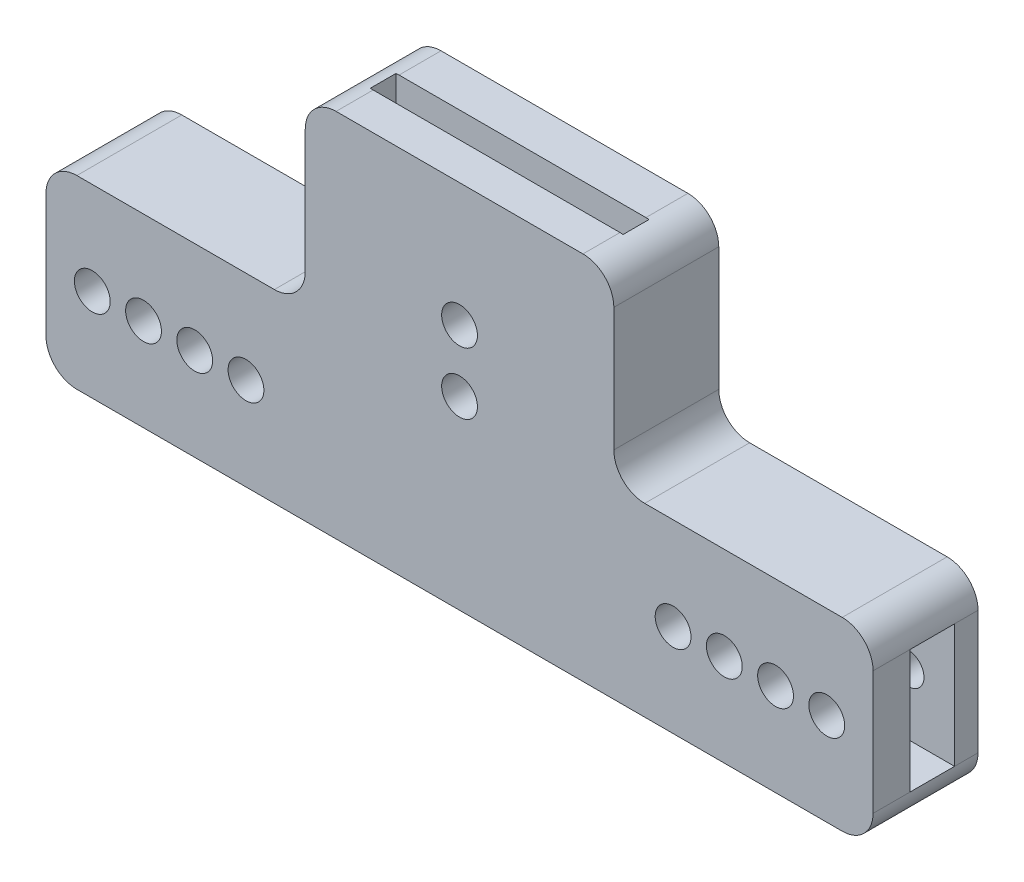
SolidWorks part; units mm, degrees
ref_plane "Front Plane" through (0, 0, 0) normal (0, 0, 1) x (1, 0, 0)
ref_plane "Top Plane" through (0, 0, 0) normal (0, 1, 0) x (1, 0, 0)
ref_plane "Right Plane" through (0, 0, 0) normal (1, 0, 0) x (0, 0, -1)
sketch "Sketch1" plane through (0, 0, 0) normal (0, 0, 1) x (1, 0, 0)
  line L1 (-25, 30) -> (25, 30)
  line L2 (-25, 30) -> (-25, -30)
  line L3 (-25, -30) -> (25, -30)
  line L4 (25, 30) -> (25, -30)
  line L5 (-25, 30) -> (25, -30) construction
  line L6 (-25, -30) -> (25, 30) construction
  point P0 (0, 0)
extrude "Boss-Extrude1" add sketch "Sketch1" along normal blind 12
sketch "Sketch2" plane through (0, 30, 0) normal (0, 1, 0) x (1, 0, 0)
  line L0 (0, 0) -> (0, -12) construction
  line L1 (-20.5, -6.8) -> (20.5, -6.8)
  line L2 (-20.5, -6.8) -> (-20.5, -11)
  line L3 (-20.5, -11) -> (20.5, -11)
  line L4 (20.5, -6.8) -> (20.5, -11)
  line L5 (-20.5, -6.8) -> (20.5, -11) construction
  line L6 (-20.5, -11) -> (20.5, -6.8) construction
  line L7 (25, 0) -> (-25, 0) construction
  line L8 (-25, -6) -> (25, -6) construction
  line L9 (-25, -12) -> (-25, 0) construction
  line L10 (25, -12) -> (25, 0) construction
  line L11 (25, -12) -> (-25, -12) construction
  point P0 (0, -8.9)
  dimension "D1" = 1
  dimension "D2" = 4.2
  dimension "D3" = 41
extrude "Cut-Extrude1" cut sketch "Sketch2" against normal through all
sketch "Sketch3" plane through (-25, 0, 0) normal (-1, 0, 0) x (0, 0, 1)
  line L0 (12, 30) -> (12, -30) construction
  line L1 (0, -30) -> (12, -30)
  line L2 (0, -30) -> (0, 0)
  line L3 (0, 0) -> (12, 0)
  line L4 (12, -30) -> (12, 0)
  line L5 (6, 0) -> (6, -30) construction
  line L6 (0, -15) -> (12, -15) construction
  point P1024 (6, -15)
  dimension "D1" = 30
extrude "Boss-Extrude2" add sketch "Sketch3" along normal blind 42
sketch "Sketch4" plane through (-67, 0, 0) normal (-1, 0, 0) x (0, 0, 1)
  line L0 (12, 0) -> (0, 0) construction
  line L1 (3.8, -5) -> (11, -5)
  line L2 (3.8, -5) -> (3.8, -25)
  line L3 (3.8, -25) -> (11, -25)
  line L4 (11, -5) -> (11, -25)
  line L5 (3.8, -5) -> (11, -25) construction
  line L6 (3.8, -25) -> (11, -5) construction
  line L7 (12, -30) -> (12, 0) construction
  line L9 (0, -30) -> (12, -30) construction
  line L10 (6, 0) -> (6, -30) construction
  point P0 (7.4, -15)
  dimension "D1" = 5
  dimension "D2" = 1
  dimension "D3" = 7.2
  dimension "D4" = 5
extrude "Cut-Extrude2" cut sketch "Sketch4" against normal blind 42.5
sketch "Sketch5" plane through (0, 0, 12) normal (0, 0, 1) x (1, 0, 0)
  line L0 (-67, -5) -> (-67, -25) construction
  circle A0 centre (-59.5, -14.9958) radius 2.55
  circle A1 centre (-51.2, -14.9958) radius 2.55
  circle A2 centre (-42.9, -14.9958) radius 2.55
  circle A3 centre (-34.6, -14.9958) radius 2.55
  dimension "D1" = 4
  dimension "D3" = 5.1
  dimension "D2" = 7.5
extrude "Cut-Extrude3" cut sketch "Sketch5" against normal blind 35
mirror "Mirror1" about plane through (0, 0, 0) normal (1, 0, 0) of "Cut-Extrude3", "Cut-Extrude2", "Boss-Extrude2"
fillet "Fillet1" radius 5 8 edges at (67, -30, 6) (67, 0, 6) (25, 0, 6) (-67, -30, 6) (-67, 0, 6) (-25, 0, 6) (25, 30, 6) (-25, 30, 6)
sketch "Sketch6" plane through (0, 0, 12) normal (0, 0, 1) x (1, 0, 0)
  circle A0 centre (0, 0) radius 2.55
  circle A1 centre (0, 10) radius 2.55
  dimension "D1" = 10
extrude "Cut-Extrude4" cut sketch "Sketch6" against normal blind 35
sketch "Sketch7" plane through (0, 0, 12) normal (0, 0, 1) x (1, 0, 0)
  line L0 (-30, 0) -> (-62, 0)
  line L1 (-67, -5) -> (-67, -25)
  line L2 (-62, -30) -> (62, -30)
  line L3 (67, -25) -> (67, -5)
  line L4 (62, 0) -> (30, 0)
  line L5 (25, 5) -> (25, 25)
  line L6 (20, 30) -> (-20, 30)
  circle A0 centre (0, 0) radius 2.9
  circle A1 centre (0, 10) radius 2.9
  circle A2 centre (34.6, -14.9958) radius 2.9
  circle A3 centre (42.9, -14.9958) radius 2.9
  circle A4 centre (51.2, -14.9958) radius 2.9
  circle A5 centre (59.5, -14.9958) radius 2.9
  circle A6 centre (-34.6, -14.9958) radius 2.9
  circle A7 centre (-42.9, -14.9958) radius 2.9
  circle A8 centre (-51.2, -14.9958) radius 2.9
  circle A9 centre (-59.5, -14.9958) radius 2.9
  arc A10 (-20, 30) -> (-24.8892, 26.0468) centre (-20, 25) ccw
  arc A11 (-20, 30) -> (-25, 25) centre (-20, 25) ccw construction
  arc A12 (-62, 0) -> (-67, -5) centre (-62, -5) ccw
  arc A13 (-67, -25) -> (-62, -30) centre (-62, -25) ccw
  arc A14 (62, -30) -> (67, -25) centre (62, -25) ccw
  arc A15 (67, -5) -> (62, 0) centre (62, -5) ccw
  arc A16 (25, 25) -> (20, 30) centre (20, 25) ccw
  arc A17 (25, 5) -> (30, 0) centre (30, 5) ccw
  line M15 (-62, -30) -> (62, -30)
  arc M16 (62, -30) -> (67, -25) centre (62, -25) ccw
  line M17 (67, -25) -> (67, -5)
  arc M18 (67, -5) -> (62, 0) centre (62, -5) ccw
  line M19 (62, 0) -> (30, 0)
  arc M20 (30, 0) -> (25, 5) centre (30, 5) cw
  line M21 (25, 5) -> (25, 25)
  arc M22 (25, 25) -> (20, 30) centre (20, 25) ccw
  line M23 (20, 30) -> (-20, 30)
  arc M24 (-20, 30) -> (-25, 25) centre (-20, 25) ccw
  line M25 (-25, 25) -> (-25, 5)
  arc M26 (-25, 5) -> (-30, 0) centre (-30, 5) cw
  line M27 (-30, 0) -> (-62, 0)
  arc M28 (-62, 0) -> (-67, -5) centre (-62, -5) ccw
  line M29 (-67, -5) -> (-67, -25)
  arc M30 (-67, -25) -> (-62, -30) centre (-62, -25) ccw
  dimension "D1" = 5.8
extrude "Boss-Extrude3" add sketch "Sketch7" along normal blind 5 contours A9 A8 A7 A6 A5 A4 A3 A2 A1 A0 M30 M15 M16 M17 M18 M19 M20 M21 M22 M23 M24 M25 M26 M27 M28 M29 region at (0, -6.6619, 12)
